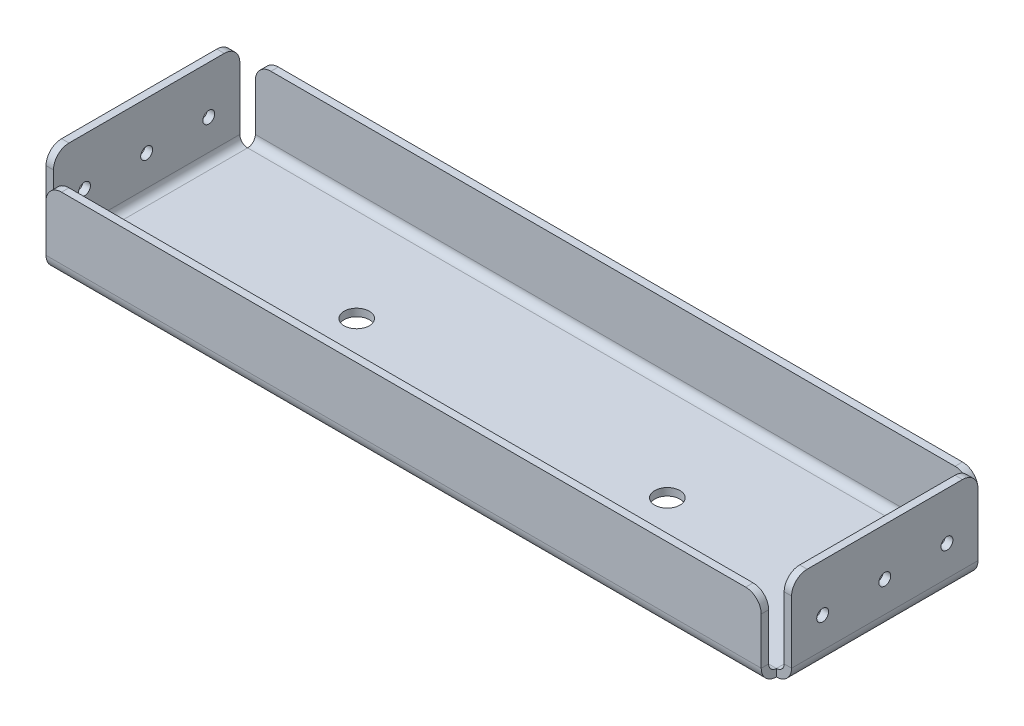
SolidWorks part; units mm, degrees
note: The reader was unsure of these and kept them because the rebuilt part matched: flange length of "Edge-Flange1", "Edge-Flange2".
ref_plane "Front Plane" through (0, 0, 0) normal (0, 0, 1) x (1, 0, 0)
ref_plane "Top Plane" through (0, 0, 0) normal (0, 1, 0) x (1, 0, 0)
ref_plane "Right Plane" through (0, 0, 0) normal (1, 0, 0) x (0, 0, -1)
sketch "Sketch1" plane through (0, 0, 0) normal (0, 1, 0) x (1, 0, 0)
  line L1 (0, 0) -> (304.8, 0)
  line L2 (0, 0) -> (0, 76.2)
  line L3 (0, 76.2) -> (304.8, 76.2)
  line L4 (304.8, 0) -> (304.8, 76.2)
  dimension "D1" = 304.8
  dimension "D2" = 76.2
base flange "Base-Flange1" sketch "Sketch1" thickness 3.0378 reverse thickness direction no parameters "D1"=3.175
edge flange "Edge-Flange1" sketch "Sketch10" flange profiles "Sketch10", "Sketch11" flange angle 90 flange length 38.1 flange position material inside bend radius 3.175 thickness 3.0378 parameters "D1"=3.81, "D6"=10, "D8"=1
sketch "Sketch10" plane through (0, 0, 0) normal (-1, 0, 0) x (0, 0, 1)
  line L2 (-76.2, 0) -> (-76.2, 35.0622)
  line L3 (-76.2, 35.0622) -> (0, 35.0622)
  line L4 (0, 35.0622) -> (0, 0)
  line L7 (-76.2, 0) -> (0, 0) construction
  line L8 (-76.2, 0) -> (0, 0)
sketch "Sketch11" plane through (304.8, 0, 0) normal (1, 0, 0) x (0, 0, -1)
  line L2 (0, 0) -> (0, 35.0622)
  line L3 (0, 35.0622) -> (76.2, 35.0622)
  line L4 (76.2, 35.0622) -> (76.2, 0)
  line L7 (0, 0) -> (76.2, 0) construction
  line L8 (0, 0) -> (76.2, 0)
bend "EdgeBend1" bend radius 3.175 bend angle 90 parameters "D5"=1
bend "EdgeBend2" bend radius 3.175 bend angle 90 parameters "D5"=2
edge flange "Edge-Flange2" sketch "Sketch16" flange profiles "Sketch16", "Sketch17" flange angle 90 flange length 31.75 flange position bend outside bend radius 3.175 thickness 3.0378 parameters "D1"=3.81, "D6"=10, "D8"=1
sketch "Sketch16" plane through (0, 0, 0) normal (0, 0, 1) x (1, 0, 0)
  line L0 (6.2128, 0) -> (298.5872, 0) construction
  line L1 (6.2128, 0) -> (298.5872, 0)
  line L2 (6.2128, 0) -> (6.2128, 28.7122)
  line L3 (6.2128, 28.7122) -> (298.5872, 28.7122)
  line L4 (298.5872, 28.7122) -> (298.5872, 0)
sketch "Sketch17" plane through (0, 0, -76.2) normal (0, 0, -1) x (-1, 0, 0)
  line L0 (-298.5872, 0) -> (-6.2128, 0) construction
  line L1 (-298.5872, 0) -> (-6.2128, 0)
  line L2 (-298.5872, 0) -> (-298.5872, 28.7122)
  line L3 (-298.5872, 28.7122) -> (-6.2128, 28.7122)
  line L4 (-6.2128, 28.7122) -> (-6.2128, 0)
bend "EdgeBend3" bend radius 3.175 bend angle 90 parameters "D5"=3
bend "EdgeBend4" bend radius 3.175 bend angle 90 parameters "D5"=4
hole_wizard "3/8 Clearance Hole1" positions "Sketch18" profile "Sketch19" hole size "3/8" standard "ANSI Inch" end condition through all
sketch "Sketch18" plane through (0, -3.0378, 0) normal (0, -1, 0) x (-1, 0, 0)
  line L2 (-298.5872, 76.2) -> (-6.2128, 76.2) construction
  line L3 (-152.4, 76.2) -> (-152.4, 0) construction
  line L4 (-6.2128, 0) -> (-298.5872, 0) construction
  line L5 (-6.2128, 0) -> (-6.2128, 76.2) construction
  point P0 (-88.9, 38.1)
  point P2 (-215.9, 38.1)
  dimension "D1" = 63.5
  dimension "D2" = 127
  dimension "D3" = 38.1
  dimension "D4" = 82.6872
sketch "Sketch19" plane through (88.9, -3.0378, -38.1) normal (1, 0, 0) x (0, 0, -1)
  line L0 (0, 0) -> (0, 38.1)
  line L1 (0, 38.1) -> (5.1587, 38.1)
  line L2 (5.1587, 38.1) -> (5.1587, 0)
  line L5 (5.1587, 0) -> (0, 0)
  line L11 (0, -6.35) -> (0, 107.95) construction
  dimension "Thru Hole Dia." = 10.3175
  dimension "Thru Hole Depth" = 38.1
hole_wizard "#11 (0.191) Diameter Hole1" positions "Sketch22" profile "Sketch23" hole size "#11" standard "ANSI Inch" end condition through all
sketch "Sketch22" plane through (304.8, 0, 0) normal (1, 0, 0) x (0, 0, -1)
  line L0 (63.5, 15.6337) -> (12.7, 15.6337) construction
  line L2 (76.2, 35.0622) -> (0, 35.0622) construction
  line L3 (0, 35.0622) -> (0, 3.175) construction
  line L4 (38.1, 35.0622) -> (38.1, 3.175) construction
  line L5 (76.2, 3.175) -> (0, 3.175) construction
  line L8 (76.2, 3.175) -> (76.2, 35.0622) construction
  point P0 (12.7, 15.6337)
  point P2 (38.1, 15.6337)
  point P4 (63.5, 15.6337)
  dimension "D1" = 19.4285
  dimension "D2" = 12.7
  dimension "D3" = 12.7
  dimension "D4" = 25.4
sketch "Sketch23" plane through (304.8, 15.6337, -12.7) normal (0, 1, 0) x (0, 0, -1)
  line L0 (0, 0) -> (0, 304.8)
  line L1 (0, 304.8) -> (2.4257, 304.8)
  line L2 (2.4257, 304.8) -> (2.4257, 0)
  line L5 (2.4257, 0) -> (0, 0)
  line L11 (0, -6.35) -> (0, 107.95) construction
  dimension "Thru Hole Dia." = 4.8514
  dimension "Thru Hole Depth" = 304.8
fillet "Fillet1" radius 6.35
sketch "Bend-Lines1" [suppressed] plane through (0, 0, 0) normal (0, 1, 0) x (1, 0, 0)
sketch "Bounding-Box1" [suppressed] plane through (0, 0, 0) normal (0, 1, 0) x (1, 0, 0)
sheet metal parameters "Sheet-Metal1" thickness 3.0378 parameters "D1"=3.81
flat pattern "Flat-Pattern1" [suppressed]
sketch "Bend-Lines2" plane through (0, 0, 0) normal (0, 1, 0) x (1, 0, 0)
sketch3d "Bounding-Box2" [suppressed]
  line L0 (-304.8, 76.2, 0) -> (0, 76.2, 0) construction
  line L1 (-304.8, 0, 0) -> (0, 0, 0) construction
  line L2 (-304.8, 76.2, 0) -> (-304.8, 0, 0) construction
  line L3 (0, 76.2, 0) -> (0, 0, 0) construction
sheet metal parameters "Sheet-Metal2" thickness 3.0378 parameters "D1"=3.81
flat pattern "Flat-Pattern1"
sketch "Bend-Lines2" plane through (0, 0, 0) normal (0, 1, 0) x (1, 0, 0)
  line L0 (305.3239, 0) -> (305.3239, 76.2) construction
  line L1 (-0.5239, 76.2) -> (-0.5239, 0) construction
  line L2 (305.3239, 0) -> (305.3239, 76.2) construction
  line L3 (-0.5239, 76.2) -> (-0.5239, 0) construction
sketch3d "Bounding-Box2" [suppressed]
  line L0 (340.5316, 76.2, 0) -> (-35.7316, 76.2, 0) construction
  line L1 (340.5316, 0, 0) -> (-35.7316, 0, 0) construction
  line L2 (340.5316, 76.2, 0) -> (340.5316, 0, 0) construction
  line L3 (-35.7316, 76.2, 0) -> (-35.7316, 0, 0) construction
bend of the flat pattern "Flatten-<EdgeBend1>1"
bend of the flat pattern "Flatten-<EdgeBend2>1"
sheet metal parameters "Sheet-Metal3" thickness 3.0378 parameters "D1"=3.81
flat pattern "Flat-Pattern1"
sketch "Bend-Lines2" plane through (0, 0, 0) normal (0, 1, 0) x (1, 0, 0)
  line L0 (301.9076, 0) -> (301.9076, 76.2) construction
  line L1 (2.8924, 76.2) -> (2.8924, 0) construction
  line L2 (301.9076, 0) -> (301.9076, 76.2) construction
  line L3 (2.8924, 76.2) -> (2.8924, 0) construction
  line L4 (297.5737, 80.5339) -> (7.2263, 80.5339) construction
  line L5 (7.2263, -4.3339) -> (297.5737, -4.3339) construction
  line L6 (297.5737, 80.5339) -> (7.2263, 80.5339) construction
  line L7 (7.2263, -4.3339) -> (297.5737, -4.3339) construction
sketch3d "Bounding-Box2" [suppressed]
  line L0 (337.1153, 109.3916, 0) -> (-32.3153, 109.3916, 0) construction
  line L1 (337.1153, -33.1916, 0) -> (-32.3153, -33.1916, 0) construction
  line L2 (337.1153, 109.3916, 0) -> (337.1153, -33.1916, 0) construction
  line L3 (-32.3153, 109.3916, 0) -> (-32.3153, -33.1916, 0) construction
bend of the flat pattern "Flatten-<EdgeBend1>1"
bend of the flat pattern "Flatten-<EdgeBend2>1"
bend of the flat pattern "Flatten-<EdgeBend3>1"
bend of the flat pattern "Flatten-<EdgeBend4>1"
sheet metal parameters "Sheet-Metal4" thickness 3.0378 parameters "D1"=3.81
flat pattern "Flat-Pattern1"
sketch "Bend-Lines2" plane through (0, 0, 0) normal (0, 1, 0) x (1, 0, 0)
  line L0 (301.9076, 0) -> (301.9076, 76.2) construction
  line L1 (2.8924, 76.2) -> (2.8924, 0) construction
  line L2 (301.9076, 0) -> (301.9076, 76.2) construction
  line L3 (2.8924, 76.2) -> (2.8924, 0) construction
  line L4 (297.5737, 80.5339) -> (7.2263, 80.5339) construction
  line L5 (7.2263, -4.3339) -> (297.5737, -4.3339) construction
  line L6 (297.5737, 80.5339) -> (7.2263, 80.5339) construction
  line L7 (7.2263, -4.3339) -> (297.5737, -4.3339) construction
sketch3d "Bounding-Box2" [suppressed]
  line L0 (337.1153, 109.3916, 0) -> (-32.3153, 109.3916, 0) construction
  line L1 (337.1153, -33.1916, 0) -> (-32.3153, -33.1916, 0) construction
  line L2 (337.1153, 109.3916, 0) -> (337.1153, -33.1916, 0) construction
  line L3 (-32.3153, 109.3916, 0) -> (-32.3153, -33.1916, 0) construction
bend of the flat pattern "Flatten-<EdgeBend1>1"
bend of the flat pattern "Flatten-<EdgeBend2>1"
bend of the flat pattern "Flatten-<EdgeBend3>1"
bend of the flat pattern "Flatten-<EdgeBend4>1"
sheet metal parameters "Sheet-Metal5" thickness 3.0378 parameters "D1"=3.81
flat pattern "Flat-Pattern1" [suppressed]
sketch "Bend-Lines2" plane through (0, 0, 0) normal (0, 1, 0) x (1, 0, 0)
  line L0 (302.2738, 0) -> (302.2738, 76.2) construction
  line L1 (2.5262, 76.2) -> (2.5262, 0) construction
  line L2 (302.2738, 0) -> (302.2738, 76.2) construction
  line L3 (2.5262, 76.2) -> (2.5262, 0) construction
  line L4 (298.5872, 79.8866) -> (6.2128, 79.8866) construction
  line L5 (6.2128, -3.6866) -> (298.5872, -3.6866) construction
  line L6 (298.5872, 79.8866) -> (6.2128, 79.8866) construction
  line L7 (6.2128, -3.6866) -> (298.5872, -3.6866) construction
sketch3d "Bounding-Box2" [suppressed]
  line L0 (-33.0475, 109.1103, 0) -> (337.8475, 109.1104, 0) construction
  line L1 (-33.0475, -32.9104, 0) -> (337.8475, -32.9103, 0) construction
  line L2 (-33.0475, 109.1103, 0) -> (-33.0475, -32.9104, 0) construction
  line L3 (337.8475, 109.1104, 0) -> (337.8475, -32.9103, 0) construction
bend of the flat pattern "Flatten-<EdgeBend1>1"
bend of the flat pattern "Flatten-<EdgeBend2>1"
bend of the flat pattern "Flatten-<EdgeBend3>1"
bend of the flat pattern "Flatten-<EdgeBend4>1"
